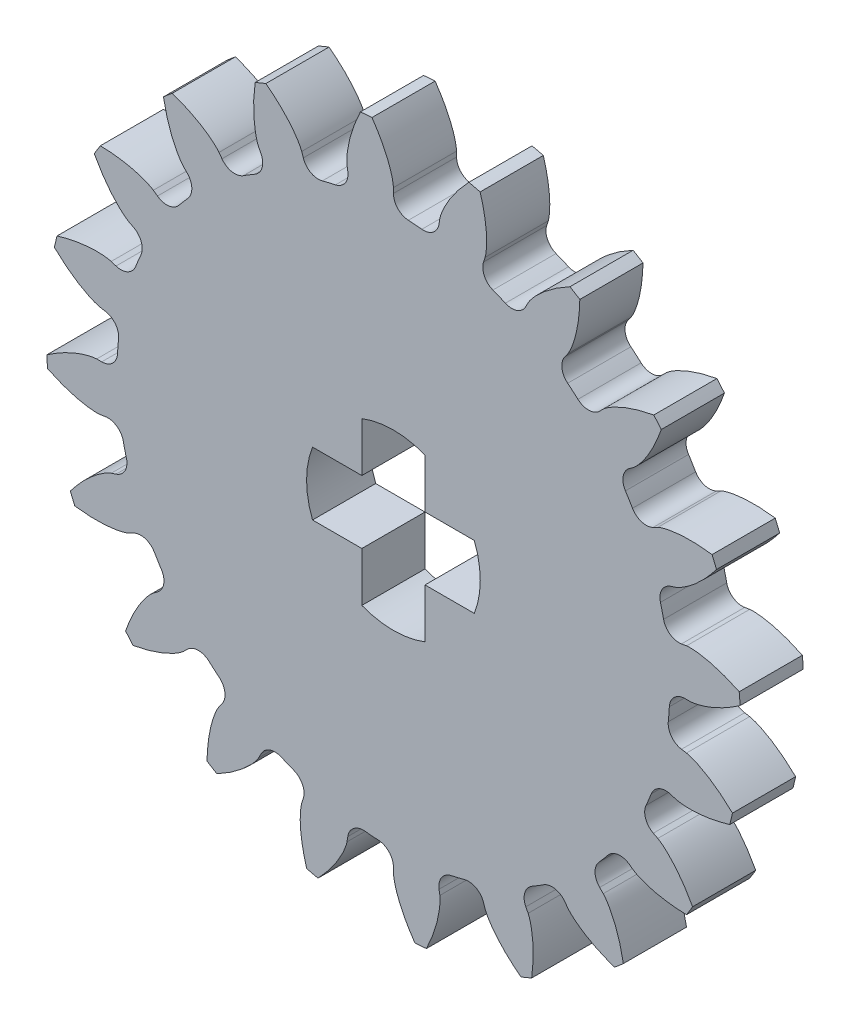
SolidWorks part; units mm, degrees
ref_plane "Plan de face" through (0, 0, 0) normal (0, 0, 1) x (1, 0, 0)
ref_plane "Plan de dessus" through (0, 0, 0) normal (0, 1, 0) x (1, 0, 0)
ref_plane "Plan de droite" through (0, 0, 0) normal (1, 0, 0) x (0, 0, -1)
sketch "Esquisse1" plane through (0, 0, 0) normal (0, 0, 1) x (1, 0, 0)
  line L0 (0, 0) -> (14, 0) construction
  line L1 (4, -8.4784) -> (4, 14.4842) construction
  line L2 (-2.6413, 18.2469) -> (12.0239, -22.0454) construction
  line L3 (14, 0) -> (45.2683, 0) construction
  line L4 (14, 0) -> (47.5962, 2.6441) construction
  line L5 (23.2812, 1.47) -> (23.1228, 1.4449)
  line L6 (23.2365, 0) -> (23.3969, 0)
  circle A0 centre (0, 0) radius 4 construction
  circle A1 centre (14, 0) radius 10 construction
  circle A2 centre (14, 0) radius 9.3969 construction
  arc A3 (22.5556, 1.834) -> (22.7372, -0.473) centre (14, 0) ccw
  arc A4 (24.979, 0.68) -> (24.9502, 1.0459) centre (14, 0) ccw
  arc A5 (23.1228, 1.4449) -> (22.5556, 1.834) centre (23.0445, 1.9387) cw
  arc A6 (23.2365, 0) -> (22.7372, -0.473) centre (23.2365, -0.5) ccw
  spline S0 degree 4 poles (23.3969, 0) (23.3999, 0) (23.4081, 0.0003) (23.4236, 0.0012) (23.449, 0.0035) (23.4812, 0.0073) (23.5228, 0.0135) (23.5717, 0.0224) (23.6252, 0.0336) (23.6833, 0.0476) (23.741, 0.0631) (23.7984, 0.0799) (23.8553, 0.0979) (23.9241, 0.1212) (24.0061, 0.1511) (24.1014, 0.1892) (24.2088, 0.2358) (24.3173, 0.287) (24.4233, 0.3405) (24.5295, 0.398) (24.6316, 0.4561) (24.7366, 0.52) (24.832, 0.5801) (24.9108, 0.6331) (24.9564, 0.6643) (24.979, 0.68) knots 0 0 0 0 0 0.005377 0.015084 0.028532 0.04661 0.064855 0.092111 0.119476 0.146842 0.174209 0.201575 0.228941 0.256307 0.307035 0.361767 0.4165 0.471232 0.525964 0.580697 0.635429 0.690161 0.744894 0.797218 0.797218 0.797218 0.797218 0.797218
  spline S2 degree 4 poles (23.2812, 1.47) (23.2841, 1.4704) (23.2923, 1.4715) (23.3078, 1.473) (23.3332, 1.4747) (23.3657, 1.4759) (23.4077, 1.4763) (23.4574, 1.4752) (23.512, 1.4725) (23.5715, 1.4678) (23.631, 1.4615) (23.6902, 1.4539) (23.7493, 1.445) (23.8208, 1.4328) (23.9066, 1.416) (24.0066, 1.3934) (24.12, 1.3641) (24.2352, 1.3305) (24.3483, 1.2943) (24.4622, 1.2541) (24.5721, 1.2127) (24.6858, 1.166) (24.7894, 1.1216) (24.8755, 1.0815) (24.9255, 1.0578) (24.9502, 1.0459) knots 0 0 0 0 0 0.005377 0.015084 0.028532 0.04661 0.064855 0.092111 0.119476 0.146842 0.174209 0.201575 0.228941 0.256307 0.307035 0.361767 0.4165 0.471232 0.525964 0.580697 0.635429 0.690161 0.744894 0.797218 0.797218 0.797218 0.797218 0.797218
  point P12 (4, 0)
  dimension "D2" = 8
  dimension "Dp" = 20
  dimension "Db" = 18.7939
  dimension "D4" = 17.5
  dimension "D5" = 22
  dimension "D7" = 0.5
  dimension "D3" = 20
  dimension "D1" = 14
  dimension "D6" = 4.5
extrude "Boss.-Extru.1" add sketch "Esquisse1" along normal blind 2
pattern_circular "Répétition circulaire1" count 20 over 360 about axis through (14, 0, 2) along (0, 0, 1) of "Boss.-Extru.1"
sketch "Esquisse2" plane through (0, 0, 2) normal (0, 0, 1) x (1, 0, 0)
  line L0 (14, -5.2181) -> (14, 4.5557) construction
  line L1 (13.2594, 0) -> (21.8469, 0) construction
  line L2 (13, 1) -> (11.4383, 1)
  line L3 (13, 2.5617) -> (13, 1)
  line L4 (15, 1) -> (15, 2.5617)
  line L5 (16.5617, 1) -> (15, 1)
  line L6 (15, -1) -> (16.5617, -1)
  line L7 (15, -2.5617) -> (15, -1)
  line L8 (13, -1) -> (13, -2.5617)
  line L9 (11.4383, -1) -> (13, -1)
  arc A0 (14, 2.75) -> (13, 2.5617) centre (14, 0) ccw
  arc A2 (11.4383, 1) -> (11.25, 0) centre (14, 0) ccw
  arc A3 (15, 2.5617) -> (14, 2.75) centre (14, 0) ccw
  arc A4 (16.75, 0) -> (16.5617, 1) centre (14, 0) ccw
  arc A5 (16.5617, -1) -> (16.75, 0) centre (14, 0) ccw
  arc A6 (14, -2.75) -> (15, -2.5617) centre (14, 0) ccw
  arc A7 (13, -2.5617) -> (14, -2.75) centre (14, 0) ccw
  arc A8 (11.25, 0) -> (11.4383, -1) centre (14, 0) ccw
  arc A9 (6.9966, 8.4825) -> (6.7175, 8.2441) centre (14, 0) ccw construction
  point P5 (17.3205, 0)
  point P34 (14, 0)
  dimension "D1" = 5.5
  dimension "D2" = 1
  dimension "D3" = 1
  dimension "D4" = 4
extrude "Enlèv. mat.-Extru.1" cut sketch "Esquisse2" against normal through all
equation "\"M\"= 1"
equation "\"Z\"= \"Dp@Esquisse1\" / \"M\""
equation "\"t\"= 1.25 * \"M\""
equation "\"e\"= \"M\" * pi / 2"
equation "\"D4@Esquisse1\"= \"Dp@Esquisse1\" - ( 2 * \"t\" )"
equation "\"D5@Esquisse1\"= \"Dp@Esquisse1\" + ( 2 * \"M\" )"
equation "\"D6@Esquisse1\"=90/\"Z\""
equation "\"D1@Répétition circulaire1\"=\"Z\""
